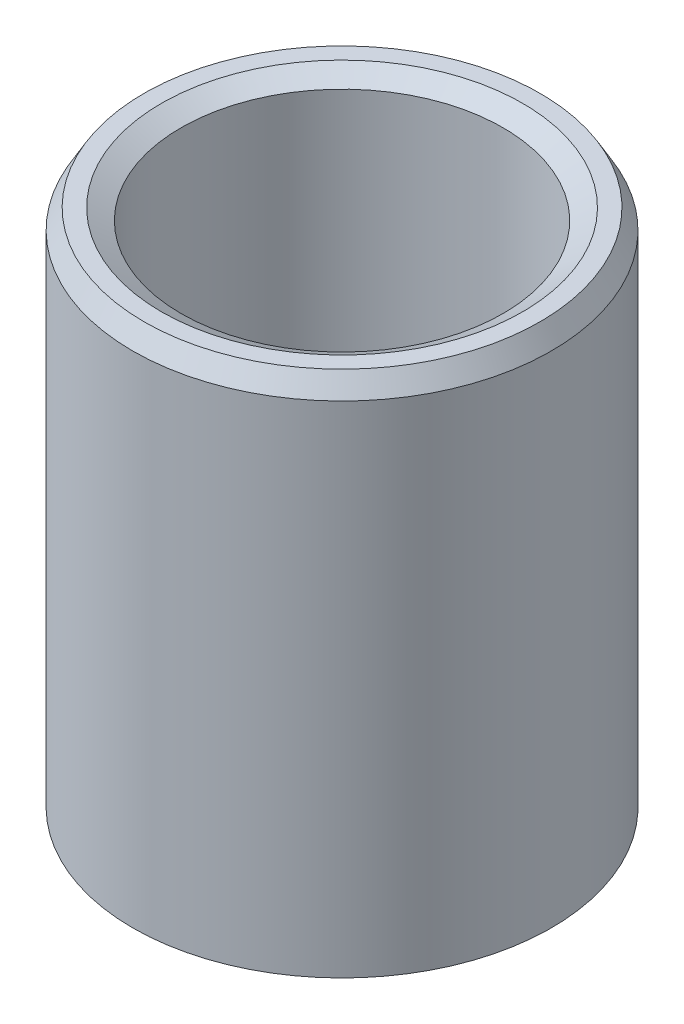
SolidWorks part; units mm, degrees
ref_plane "Front Plane" through (0, 0, 0) normal (0, 0, 1) x (1, 0, 0)
ref_plane "Top Plane" through (0, 0, 0) normal (0, 1, 0) x (1, 0, 0)
ref_plane "Right Plane" through (0, 0, 0) normal (1, 0, 0) x (0, 0, -1)
sketch "Sketch1" plane through (0, 0, 0) normal (0, 1, 0) x (1, 0, 0)
  circle A0 centre (0, 0) radius 42.5
  dimension "SLEEVE_OD" = 85
extrude "Boss-Extrude1" add sketch "Sketch1" along normal blind 107.7506
sketch "Sketch2" plane through (0, 0, 0) normal (0, 1, 0) x (1, 0, 0)
  circle A0 centre (0, 0) radius 32.6978
  dimension "BORE_D" = 65.3956
extrude "Cut-Extrude1" cut sketch "Sketch2" along normal through all
chamfer "Chamfer1" distance 3.9824 angle 30 4 edges at (0, 107.7506, 32.6978) (0, 0, 32.6978) (0, 0, 42.5) (0, 107.7506, 42.5) first distance on face at (0, 107.7506, 32.6978) first distance on face at (0, 0, 32.6978) first distance on face at (0, 107.7506, 42.5)
